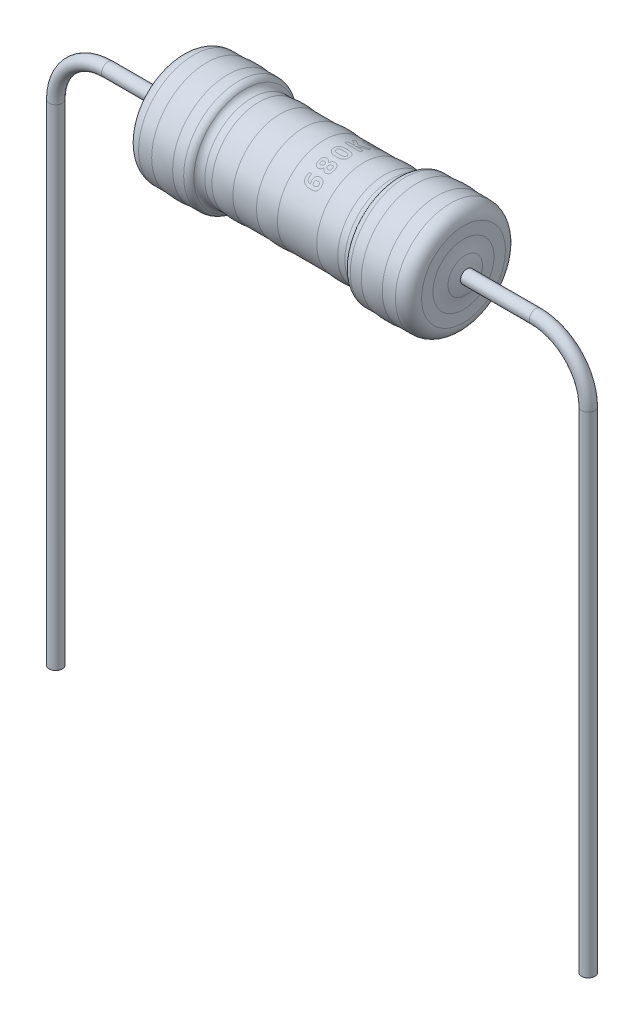
SolidWorks part; units mm, degrees
ref_plane "Front Plane" through (0, 0, 0) normal (0, 0, 1) x (1, 0, 0)
ref_plane "Top Plane" through (0, 0, 0) normal (0, 1, 0) x (1, 0, 0)
ref_plane "Right Plane" through (0, 0, 0) normal (1, 0, 0) x (0, 0, -1)
sketch "Sketch Set Wire Width" plane through (0, 0, 0) normal (0, 0, 1) x (1, 0, 0)
  line L0 (-8.16, 0) -> (8.16, 0)
  line L1 (-10.16, -2) -> (-10.16, -20.6984)
  line L2 (10.16, -2) -> (10.16, -20.6984)
  line L3 (-10.16, -20.6984) -> (10.16, -20.6984) construction
  line L4 (0, 0) -> (0, -20.6984) construction
  arc A0 (-8.16, 0) -> (-10.16, -2) centre (-8.16, -2) ccw
  arc A1 (8.16, 0) -> (10.16, -2) centre (8.16, -2) cw
  dimension "D2" = 2
  dimension "D3" = 60
  dimension "D1" = 20.32
sketch "Sketch Wire Diameter" plane through (0, 0, 0) normal (1, 0, 0) x (0, 0, -1)
  circle A0 centre (0, 0) radius 0.25
  dimension "D1" = 0.5
sweep "SET WIRE LENGTH" add profiles "Sketch Wire Diameter" path "Sketch Set Wire Width"
sketch "Sketch3" plane through (0, 0, 0) normal (0, 0, 1) x (1, 0, 0)
  line L0 (-5.4, 0) -> (5.4, 0)
  line L1 (0, 0) -> (0, 1.8) construction
  line L2 (-2.9, 1.8) -> (2.9, 1.8)
  line L3 (-5.4, 0) -> (-5.4, 1.6)
  line L4 (-4.9, 2.1) -> (-3.18, 2.1)
  line L5 (-2.9, 1.82) -> (-2.9, 1.8)
  line L6 (5.4, 0) -> (5.4, 1.6)
  line L7 (4.9, 2.1) -> (3.18, 2.1)
  line L8 (2.9, 1.82) -> (2.9, 1.8)
  arc A0 (-5.4, 1.6) -> (-4.9, 2.1) centre (-4.9, 1.6) cw
  arc A1 (5.4, 1.6) -> (4.9, 2.1) centre (4.9, 1.6) ccw
  arc A2 (-3.18, 2.1) -> (-2.9, 1.82) centre (-3.18, 1.82) cw
  arc A3 (3.18, 2.1) -> (2.9, 1.82) centre (3.18, 1.82) ccw
  dimension "D5" = 0.5
  dimension "D6" = 0.28
  dimension "D1" = 10.8
  dimension "D2" = 5.8
  dimension "D3" = 1.8
  dimension "D4" = 2.1
revolve "Revolve2" add sketch "Sketch3" angle 360 about L0
fillet "Fillet1" radius 0.3 2 edges at (2.9, 0, 1.8) (-2.9, 0, 1.8)
sketch "Sketch5" plane through (0, 0, 0) normal (0, 0, 1) x (1, 0, 0)
  line L0 (0, 0) -> (2, 0) construction
  line L1 (0, 0) -> (-0.3, 0) construction
  line L2 (-0.3, 0) -> (-2, 0) construction
  line L3 (-2, 0) -> (-4, 0) construction
  line L4 (2, 0) -> (4, 0) construction
  line L5 (-4, 0) -> (-4, 2.1) construction
  line L6 (-0.3, 0) -> (-0.3, 1.8) construction
  line L7 (-2, 0) -> (-2, 1.8) construction
  line L8 (2, 0) -> (2, 1.8) construction
  line L9 (4, 0) -> (4, 2.1) construction
  line L10 (-4, 2.1) -> (-4, 2.13) construction
  line L11 (-4.9, 2.1) -> (-3.18, 2.1) construction
  line L12 (4.9, 2.1) -> (3.18, 2.1) construction
  line L13 (-2.9, 1.8) -> (2.9, 1.8) construction
  line L14 (-2, 1.8) -> (-2, 1.83) construction
  line L17 (-4.4, 2.1) -> (-3.6, 2.1)
  line L19 (-5.4, 0) -> (5.4, 0) construction
  line L22 (-2.4, 1.8) -> (-1.6, 1.8) construction
  line L26 (-0.7, 1.8) -> (0.1, 1.8) construction
  line L30 (1.6, 1.8) -> (2.4, 1.8) construction
  line L34 (3.6, 2.1) -> (4.4, 2.1) construction
  line L36 (-0.3, 1.8) -> (-0.3, 1.83) construction
  line L37 (2, 1.8) -> (2, 1.83) construction
  line L38 (4, 2.1) -> (4, 2.13) construction
  arc A0 (-4.4, 2.1) -> (-3.6, 2.1) centre (-4, -0.5517) cw
  arc A1 (-2.4, 1.8) -> (-1.6, 1.8) centre (-2, -0.8517) cw construction
  arc A2 (-0.7, 1.8) -> (0.1, 1.8) centre (-0.3, -0.8517) cw construction
  arc A3 (1.6, 1.8) -> (2.4, 1.8) centre (2, -0.8517) cw construction
  arc A4 (3.6, 2.1) -> (4.4, 2.1) centre (4, -0.5517) cw construction
  dimension "D3" = 0.8
  dimension "D1" = 4
  dimension "D2" = 4
  dimension "D4" = 0.03
  dimension "D5" = 2
  dimension "D6" = 2
  dimension "D7" = 1.7
revolve "Band 1" add sketch "Sketch5" angle 360 about L2
sketch "Sketch8" plane through (0, 0, 0) normal (0, 0, 1) x (1, 0, 0)
  line L0 (-2.4, 1.8) -> (-1.6, 1.8) construction
  line L1 (-2.4, 1.8) -> (-1.6, 1.8)
  arc A0 (-1.6, 1.8) -> (-2.4, 1.8) centre (-2, -0.8517) ccw construction
  arc A1 (-1.6, 1.8) -> (-2.4, 1.8) centre (-2, -0.8517) ccw
revolve "Band 2" add sketch "Sketch8" angle 360 about L2
sketch "Sketch9" plane through (0, 0, 0) normal (0, 0, 1) x (1, 0, 0)
  line L0 (-0.7, 1.8) -> (0.1, 1.8) construction
  line L1 (-0.7, 1.8) -> (0.1, 1.8)
  arc A0 (0.1, 1.8) -> (-0.7, 1.8) centre (-0.3, -0.8517) ccw construction
  arc A1 (0.1, 1.8) -> (-0.7, 1.8) centre (-0.3, -0.8517) ccw
revolve "Band 3" add sketch "Sketch9" angle 360 about L2
sketch "Sketch10" plane through (0, 0, 0) normal (0, 0, 1) x (1, 0, 0)
  line L0 (1.6, 1.8) -> (2.4, 1.8) construction
  line L1 (1.6, 1.8) -> (2.4, 1.8)
  arc A0 (2.4, 1.8) -> (1.6, 1.8) centre (2, -0.8517) ccw construction
  arc A1 (2.4, 1.8) -> (1.6, 1.8) centre (2, -0.8517) ccw
revolve "Band 4" add sketch "Sketch10" angle 360 about L0
sketch "Sketch11" plane through (0, 0, 0) normal (0, 0, 1) x (1, 0, 0)
  line L0 (3.6, 2.1) -> (4.4, 2.1) construction
  line L1 (3.6, 2.1) -> (4.4, 2.1)
  arc A0 (4.4, 2.1) -> (3.6, 2.1) centre (4, -0.5517) ccw construction
  arc A1 (4.4, 2.1) -> (3.6, 2.1) centre (4, -0.5517) ccw
revolve "Band 5" add sketch "Sketch11" angle 360 about L4
sketch "Sketch12" plane through (0, 0, 0) normal (0, 0, 1) x (1, 0, 0)
  line L0 (-5.35, 0) -> (5.35, 0) construction
  line L1 (-5.35, 1) -> (-5.35, 0)
  line L2 (5.35, 1) -> (5.35, 0)
  line L3 (-5.35, 0) -> (-5.55, 0)
  line L4 (5.35, 0) -> (5.55, 0)
  arc A0 (-5.35, 1) -> (-5.55, 0) centre (-2.95, 0) ccw
  arc A1 (5.35, 1) -> (5.55, 0) centre (2.95, 0) cw
  dimension "D3" = 0.2
  dimension "D4" = 2.6
  dimension "D1" = 10.7
  dimension "D2" = 1
revolve "Revolve10" add sketch "Sketch12" angle 360 about L0
fillet "Fillet2" radius 2 2 edges at (5.4, 0, 0.8703) (-5.4, 0, -0.8703)
ref_plane "Plane2" through (0, 3, 0) normal (0, 1, 0) x (1, 0, 0)
sketch "Sketch13" plane through (0, 3, 0) normal (0, 1, 0) x (1, 0, 0)
  line L0 (0, 0) -> (1.15, 0) construction
  line L1 (1.15, 1.75) -> (1.15, -1.75) construction
  text T0 "680KΩ" font "Calibri" height 0.6
  dimension "D1" = 3.5
  dimension "D2" = 1.15
wrap "Wrap1" sketch "Sketch13" wrap type scribe source sketch "Sketch13" face at (0.1, 1.8, 0)
